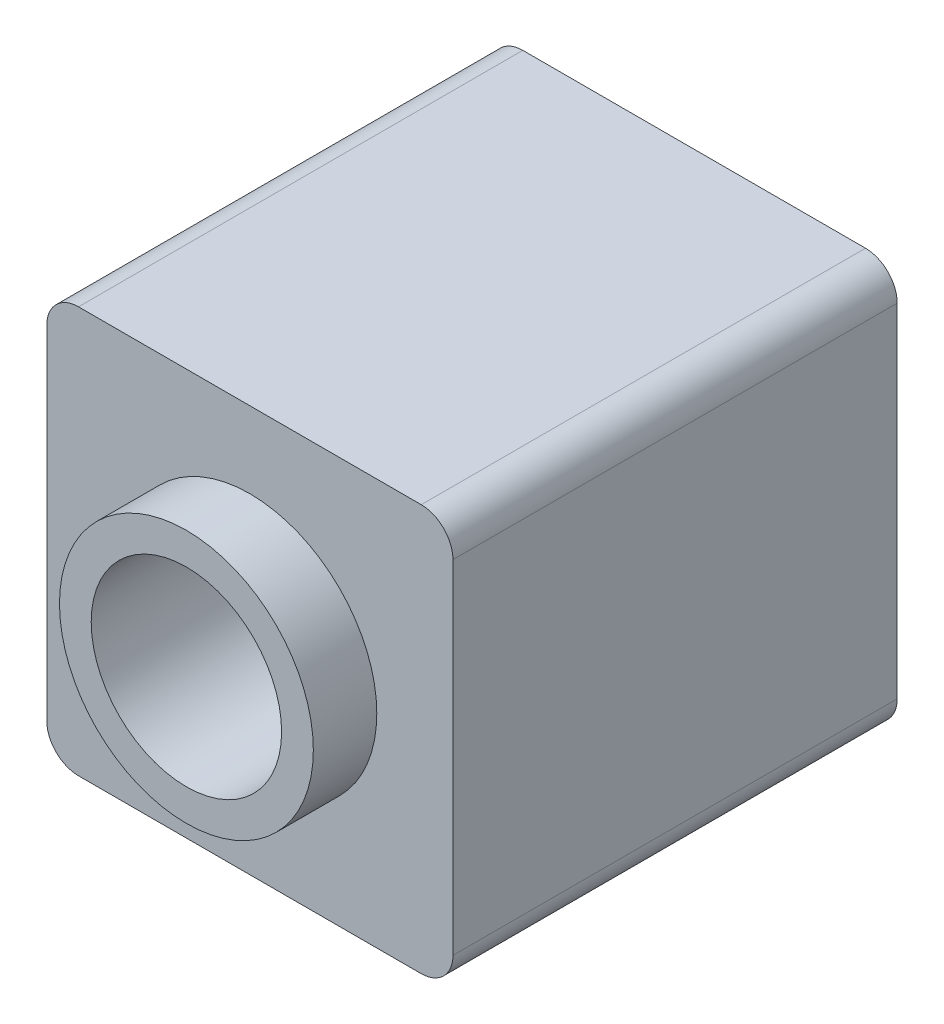
SolidWorks part; units mm, degrees
ref_plane "Front Plane" through (0, 0, 0) normal (0, 0, 1) x (1, 0, 0)
ref_plane "Top Plane" through (0, 0, 0) normal (0, 1, 0) x (1, 0, 0)
ref_plane "Right Plane" through (0, 0, 0) normal (1, 0, 0) x (0, 0, -1)
sketch "Sketch2" plane through (0, 0, -57.4655) normal (0, 0, -1) x (-1, 0, 0)
  line L1 (-6.4405, -35.0284) -> (-1.0405, -35.0284)
  line L2 (-6.9405, -34.5284) -> (-6.9405, -29.1284)
  line L3 (-6.4405, -28.6284) -> (-1.0405, -28.6284)
  line L4 (-0.5405, -34.5284) -> (-0.5405, -29.1284)
  line L5 (-6.9405, -35.0284) -> (-0.5405, -28.6284) construction
  line L6 (-6.9405, -28.6284) -> (-0.5405, -35.0284) construction
  circle A0 centre (-3.7405, -31.8284) radius 1.5
  arc A1 (-0.5405, -34.5284) -> (-1.0405, -35.0284) centre (-1.0405, -34.5284) cw
  arc A2 (-6.9405, -34.5284) -> (-6.4405, -35.0284) centre (-6.4405, -34.5284) ccw
  arc A3 (-6.9405, -29.1284) -> (-6.4405, -28.6284) centre (-6.4405, -29.1284) cw
  arc A4 (-0.5405, -29.1284) -> (-1.0405, -28.6284) centre (-1.0405, -29.1284) ccw
  point P0 (-3.7405, -31.8284)
  dimension "D2" = 3
  dimension "D3" = 0.5
  dimension "D1" = 6.4
extrude "Boss-Extrude1" add sketch "Sketch2" along normal blind 8
sketch "Sketch3" plane through (0, 0, -57.4655) normal (0, 0, -1) x (-1, 0, 0)
  line L4 (-1.0405, -28.6284) -> (-6.4405, -28.6284)
  line L5 (-6.9405, -29.1284) -> (-6.9405, -34.5284)
  line L6 (-6.4405, -35.0284) -> (-1.0405, -35.0284)
  line L7 (-0.5405, -34.5284) -> (-0.5405, -29.1284)
  line L8 (-1.0405, -28.6284) -> (-6.4405, -28.6284)
  line L9 (-6.9405, -29.1284) -> (-6.9405, -34.5284)
  line L10 (-6.4405, -35.0284) -> (-1.0405, -35.0284)
  line L11 (-0.5405, -34.5284) -> (-0.5405, -29.1284)
  circle A1 centre (-3.7405, -31.8284) radius 5 construction
  circle A2 centre (-3.7405, -31.8284) radius 2
  arc A6 (-6.4405, -28.6284) -> (-6.9405, -29.1284) centre (-6.4405, -29.1284) ccw
  arc A7 (-6.9405, -34.5284) -> (-6.4405, -35.0284) centre (-6.4405, -34.5284) ccw
  arc A8 (-1.0405, -35.0284) -> (-0.5405, -34.5284) centre (-1.0405, -34.5284) ccw
  arc A9 (-0.5405, -29.1284) -> (-1.0405, -28.6284) centre (-1.0405, -29.1284) ccw
  arc A10 (-6.4405, -28.6284) -> (-6.9405, -29.1284) centre (-6.4405, -29.1284) ccw
  arc A11 (-6.9405, -34.5284) -> (-6.4405, -35.0284) centre (-6.4405, -34.5284) ccw
  arc A12 (-1.0405, -35.0284) -> (-0.5405, -34.5284) centre (-1.0405, -34.5284) ccw
  arc A13 (-0.5405, -29.1284) -> (-1.0405, -28.6284) centre (-1.0405, -29.1284) ccw
  dimension "D1" = 4
  dimension "D2" = 0
extrude "Cut-Extrude1" cut sketch "Sketch3" along normal blind 1
sketch "Sketch4" plane through (0, 0, -65.4655) normal (0, 0, -1) x (-1, 0, 0)
  circle A0 centre (-3.7405, -31.8284) radius 2.4
extrude "Cut-Extrude2" cut sketch "Sketch4" against normal blind 4
